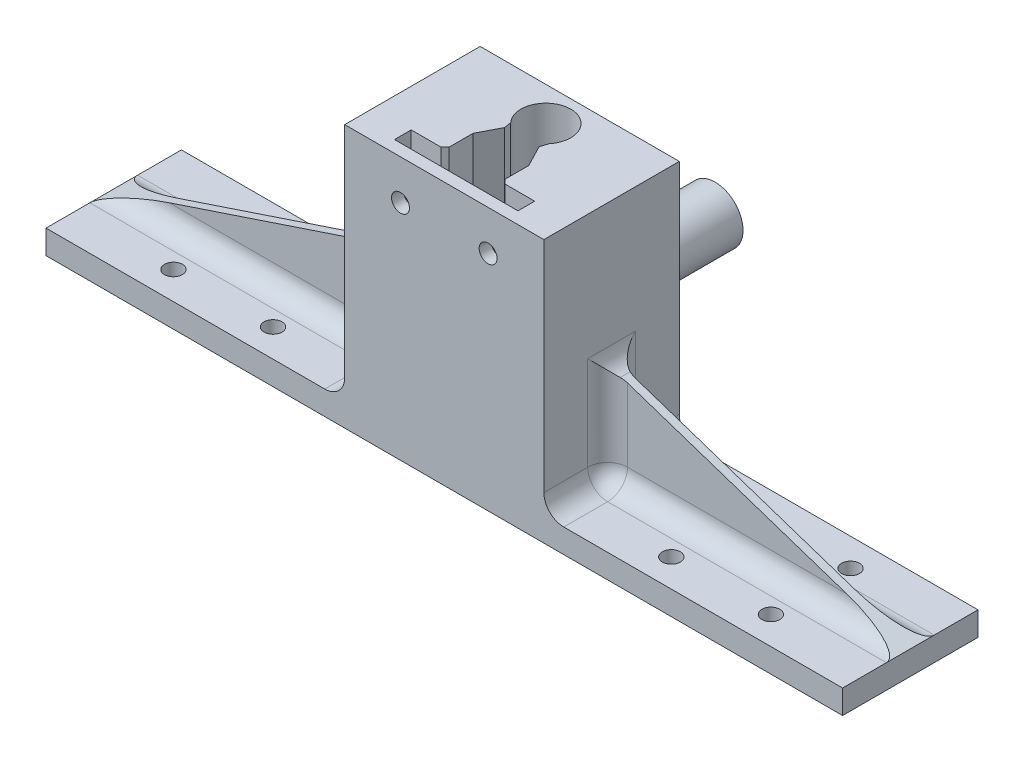
SolidWorks part; units mm, degrees
ref_plane "Front Plane" through (0, 0, 0) normal (0, 0, 1) x (1, 0, 0)
ref_plane "Top Plane" through (0, 0, 0) normal (0, 1, 0) x (1, 0, 0)
ref_plane "Right Plane" through (0, 0, 0) normal (1, 0, 0) x (0, 0, -1)
sketch "Sketch1" plane through (0, 0, 0) normal (0, 1, 0) x (1, 0, 0)
  line L1 (25, -17) -> (-25, -17)
  line L2 (25, -17) -> (25, 17)
  line L3 (25, 17) -> (-25, 17)
  line L4 (-25, -17) -> (-25, 17)
  line L5 (25, -17) -> (-25, 17) construction
  line L6 (25, 17) -> (-25, -17) construction
  point P0 (0, 0)
  dimension "D1" = 50
  dimension "D2" = 34
extrude "Boss-Extrude1" add sketch "Sketch1" along normal blind 60
sketch "Sketch2" plane through (0, 60, 0) normal (0, 1, 0) x (1, 0, 0)
  line L0 (-3.75, 3.5) -> (-7, -2.8)
  line L1 (15.5, -14) -> (-15.5, -14)
  line L2 (15.5, -14) -> (15.5, -9.8)
  line L3 (15.5, -9.8) -> (7, -9.8)
  line L4 (-15.5, -14) -> (-15.5, -9.8)
  line L5 (15.5, -14) -> (-15.5, -9.8) construction
  line L6 (15.5, -9.8) -> (-15.5, -14) construction
  line L7 (-7, -2.8) -> (-7, -9.8)
  line L8 (3.75, 3.5) -> (7, -2.8)
  line L9 (7, -2.8) -> (7, -9.8)
  line L10 (0, -1000) -> (0, 49000) construction
  line L11 (-25, -17) -> (25, -17) construction
  line L12 (-7, -9.8) -> (-15.5, -9.8)
  arc A0 (3.75, 3.5) -> (-3.75, 3.5) centre (0, 8.5) ccw
  point P2 (0, -11.9)
  dimension "D1" = 12.5
  dimension "D6" = 22.5
  dimension "D2" = 4.2
  dimension "D3" = 31
  dimension "D4" = 7
  dimension "D5" = 7.5
  dimension "D7" = 14
  dimension "D8" = 3
extrude "Cut-Extrude1" cut sketch "Sketch2" against normal through all
sketch "Sketch3" plane through (0, 0, 17) normal (0, 0, 1) x (1, 0, 0)
  line L0 (0, -1000) -> (0, 49000) construction
  line L2 (-25, 0) -> (25, 0) construction
  circle A0 centre (-11, 50) radius 2.25
  circle A1 centre (11, 50) radius 2.25
  dimension "D1" = 4.5
  dimension "D3" = 50
  dimension "D2" = 22
extrude "Cut-Extrude2" cut sketch "Sketch3" against normal through all
sketch "Sketch4" plane through (0, 0, -17) normal (0, 0, -1) x (-1, 0, 0)
  line L1 (14.75, 52.1651) -> (11, 54.3301)
  line L2 (11, 54.3301) -> (7.25, 52.1651)
  line L3 (7.25, 52.1651) -> (7.25, 47.8349)
  line L4 (7.25, 47.8349) -> (11, 45.6699)
  line L5 (11, 45.6699) -> (14.75, 47.8349)
  line L6 (14.75, 47.8349) -> (14.75, 52.1651)
  line L7 (-7.25, 47.8349) -> (-7.25, 52.1651)
  line L8 (-7.25, 52.1651) -> (-11, 54.3301)
  line L9 (-11, 54.3301) -> (-14.75, 52.1651)
  line L10 (-14.75, 52.1651) -> (-14.75, 47.8349)
  line L11 (-14.75, 47.8349) -> (-11, 45.6699)
  line L12 (-11, 45.6699) -> (-7.25, 47.8349)
  circle A0 centre (11, 50) radius 3.75 construction
  circle A1 centre (-11, 50) radius 3.75 construction
  dimension "D1" = 7.5
extrude "Cut-Extrude3" cut sketch "Sketch4" against normal offset from surface (24.8 mm away) 2 up to face at (-13.25, 50, 9.8)
chamfer "Chamfer1" distance 1 angle 45 4 edges at (7, 30, 9.8) (-7, 30, 9.8) (-3.75, 30, -3.5) (3.75, 30, -3.5) first distance on face at (8.75, 50, 9.8) first distance on face at (-7, 30, 6.3) first distance on face at (0, 30, -9.125) first distance on face at (5.375, 30, -0.35)
sketch "Sketch5" plane through (0, 0, 0) normal (0, -1, 0) x (1, 0, 0)
  line L0 (-25, 17) -> (25, 17) construction
  line L1 (100, -17) -> (-100, -17)
  line L2 (100, -17) -> (100, 17)
  line L3 (100, 17) -> (-100, 17)
  line L4 (-100, -17) -> (-100, 17)
  line L5 (100, -17) -> (-100, 17) construction
  line L6 (100, 17) -> (-100, -17) construction
  point P0 (0, 0)
  dimension "D1" = 200
extrude "Boss-Extrude2" add sketch "Sketch5" along normal blind 6
ref_plane "Plane1" through (0, 0, 0) normal (0, 0, 1) x (1, 0, 0)
sketch "Sketch6" plane through (0, 0, 0) normal (0, 0, 1) x (1, 0, 0)
  line L0 (-100, 0) -> (-25, 25)
  line L1 (-25, 60) -> (-25, 0) construction
  line L2 (-25, 25) -> (-25, 0)
  line L3 (-25, 0) -> (-100, 0)
  dimension "D1" = 25
extrude "Boss-Extrude3" add sketch "Sketch6" along normal blind 1 and the other way blind 1
mirror "Mirror3" about plane through (0, 0, 0) normal (1, 0, 0) of "Boss-Extrude3"
fillet "Fillet1" radius 5 4 edges at (-62.5, 0, -1) (-62.5, 0, 1) (62.5, 0, -1) (62.5, 0, 1)
fillet "Fillet2" radius 5 14 edges at (-25, 0, -11.5) (-25, 1.4645, -2.4645) (-25, 0, 11.5) (-25, 1.4645, 2.4645) (-25, 15, -1) (-25, 15, 1) (-25, 25, 0) (25, 0, -11.5) (25, 1.4645, -2.4645) (25, 0, 11.5) (25, 1.4645, 2.4645) (25, 15, -1) (25, 25, 0) (25, 15, 1)
sketch "Sketch7" plane through (0, -6, 0) normal (0, -1, 0) x (1, 0, 0)
  line L0 (-100, 17) -> (-100, -17) construction
  line L3 (-1000, 0) -> (49000, 0) construction
  circle A0 centre (-75, 10) radius 2.25
  circle A1 centre (-75, -10) radius 2.25
  dimension "D2" = 4.5
  dimension "D1" = 25
  dimension "D3" = 20
extrude "Cut-Extrude4" cut sketch "Sketch7" against normal blind 4
sketch "Sketch8" plane through (0, -2, 0) normal (0, -1, 0) x (-1, 0, 0)
  circle A0 centre (75, -10) radius 2.25
  circle A1 centre (75, 10) radius 2.25
  dimension "D1" = 4.5
extrude "Cut-Extrude5" cut sketch "Sketch8" against normal through all
pattern_linear "LPattern1" count 2 spacing 25 along (1, 0, 0) of "Cut-Extrude4", "Cut-Extrude5"
mirror "Mirror4" about plane through (0, 0, 0) normal (1, 0, 0) of "LPattern1", "Cut-Extrude5", "Cut-Extrude4"
sketch "Sketch9" plane through (0, 0, 0) normal (0, 1, 0) x (1, 0, 0)
  line L13 (4.2085, 2.6113) -> (4.8175, 4.5183)
  line L14 (-4.5694, 4.2358) -> (-4.3094, 2.4157)
  line L15 (-4.3094, 2.4157) -> (-7, -2.8)
  line L16 (-7, -2.8) -> (-7, -8.8)
  line L17 (-7, -8.8) -> (-8, -9.8)
  line L18 (-8, -9.8) -> (-15.5, -9.8)
  line L19 (-15.5, -9.8) -> (-15.5, -14)
  line L20 (-15.5, -14) -> (15.5, -14)
  line L21 (15.5, -14) -> (15.5, -9.8)
  line L22 (15.5, -9.8) -> (8, -9.8)
  line L23 (8, -9.8) -> (7, -8.8)
  line L24 (7, -8.8) -> (7, -2.8)
  line L25 (7, -2.8) -> (4.2085, 2.6113)
  line L26 (4.2085, 2.6113) -> (4.8175, 4.5183)
  line L27 (-4.5694, 4.2358) -> (-4.3094, 2.4157)
  line L28 (-4.3094, 2.4157) -> (-7, -2.8)
  line L29 (-7, -2.8) -> (-7, -8.8)
  line L30 (-7, -8.8) -> (-8, -9.8)
  line L31 (-8, -9.8) -> (-15.5, -9.8)
  line L32 (-15.5, -9.8) -> (-15.5, -14)
  line L33 (-15.5, -14) -> (15.5, -14)
  line L34 (15.5, -14) -> (15.5, -9.8)
  line L35 (15.5, -9.8) -> (8, -9.8)
  line L36 (8, -9.8) -> (7, -8.8)
  line L37 (7, -8.8) -> (7, -2.8)
  line L38 (7, -2.8) -> (4.2085, 2.6113)
  arc A1 (4.8175, 4.5183) -> (-4.5694, 4.2358) centre (0, 8.5) ccw
  arc A2 (4.8175, 4.5183) -> (-4.5694, 4.2358) centre (0, 8.5) ccw
  dimension "D1" = 0
extrude "Cut-Extrude6" cut sketch "Sketch9" against normal blind 4
sketch "Sketch10" plane through (0, 0, -17) normal (0, 0, -1) x (-1, 0, 0)
  line L0 (100, -6) -> (-100, -6) construction
  circle A0 centre (0, 19) radius 7
  point P5 (0, 0)
  dimension "D1" = 14
  dimension "D2" = 25
extrude "Boss-Extrude4" add sketch "Sketch10" along normal blind 14
sketch "Sketch11" plane through (0, 0, -31) normal (0, 0, -1) x (-1, 0, 0)
  circle A0 centre (0, 19) radius 7
  circle A1 centre (0, 19) radius 4.15
  circle A2 centre (0, 19) radius 7 construction
  dimension "D1" = 8.3
extrude "Boss-Extrude5" add sketch "Sketch11" along normal blind 20
chamfer "Chamfer2" distance 10 angle 1 1 edges at (-4.15, 19, -31) first distance on face at (-4.15, 19, -51)
chamfer "Chamfer3" distance 10 angle 45 1 edges at (7, 19, -17)
